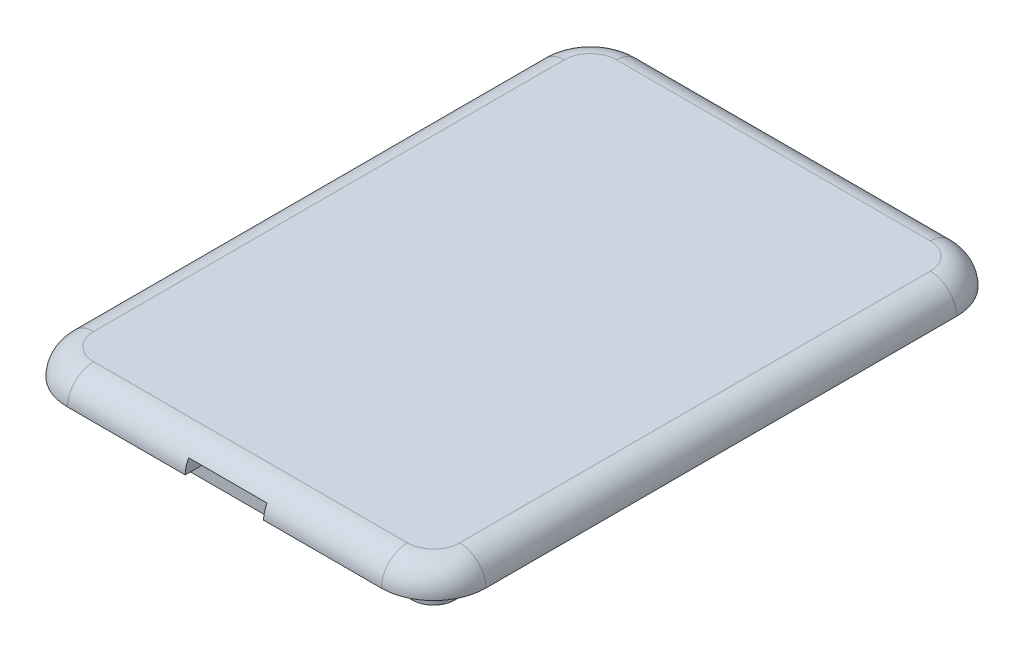
SolidWorks part; units mm, degrees
ref_plane "Front Plane" through (0, 0, 0) normal (0, 0, 1) x (1, 0, 0)
ref_plane "Top Plane" through (0, 0, 0) normal (0, 1, 0) x (1, 0, 0)
ref_plane "Right Plane" through (0, 0, 0) normal (1, 0, 0) x (0, 0, -1)
sketch "Sketch1" plane through (0, 0, 0) normal (0, 1, 0) x (1, 0, 0)
  line L0 (-45.2395, 52.3807) -> (-45.2395, -61.9193)
  line L1 (-40.1595, 65.0807) -> (36.0405, 65.0807)
  line L2 (-52.8595, 52.3807) -> (-52.8595, -61.9193)
  line L3 (-40.1595, -74.6193) -> (36.0405, -74.6193)
  line L4 (48.7405, 52.3807) -> (48.7405, -61.9193)
  line L5 (-40.1595, -66.9993) -> (36.0405, -66.9993)
  line L6 (41.1205, 52.3807) -> (41.1205, -61.9193)
  line L7 (-40.1595, 57.4607) -> (36.0405, 57.4607)
  line L8 (-37.6195, 49.8407) -> (-37.6195, -59.3793)
  line L9 (-37.6195, -59.3793) -> (33.5005, -59.3793)
  line L10 (33.5005, 49.8407) -> (33.5005, -59.3793)
  line L11 (-37.6195, 49.8407) -> (33.5005, 49.8407)
  arc A0 (-52.8595, -61.9193) -> (-40.1595, -74.6193) centre (-40.1595, -61.9193) ccw
  arc A1 (36.0405, -74.6193) -> (48.7405, -61.9193) centre (36.0405, -61.9193) ccw
  arc A2 (36.0405, 65.0807) -> (48.7405, 52.3807) centre (36.0405, 52.3807) cw
  arc A3 (-40.1595, 65.0807) -> (-52.8595, 52.3807) centre (-40.1595, 52.3807) ccw
  arc A4 (-45.2395, -61.9193) -> (-40.1595, -66.9993) centre (-40.1595, -61.9193) ccw
  arc A5 (36.0405, -66.9993) -> (41.1205, -61.9193) centre (36.0405, -61.9193) ccw
  arc A6 (36.0405, 57.4607) -> (41.1205, 52.3807) centre (36.0405, 52.3807) cw
  arc A7 (-40.1595, 57.4607) -> (-45.2395, 52.3807) centre (-40.1595, 52.3807) ccw
  arc A8 (-37.6195, -59.3793) -> (-37.6195, -59.3793) centre (-37.6195, -59.3793) ccw
  arc A9 (33.5005, -59.3793) -> (33.5005, -59.3793) centre (33.5005, -59.3793) ccw
  arc A10 (33.5005, 49.8407) -> (33.5005, 49.8407) centre (33.5005, 49.8407) cw
  arc A11 (-37.6195, 49.8407) -> (-37.6195, 49.8407) centre (-37.6195, 49.8407) ccw
  point P6 (-52.8595, -74.6193)
  point P9 (48.7405, -74.6193)
  point P14 (-52.8595, 65.0807)
  dimension "D3" = 12.7
  dimension "D1" = 139.7
  dimension "D2" = 101.6
  dimension "D4" = 7.62
  dimension "D5" = 7.62
extrude "Boss-Extrude1" add sketch "Sketch1" against normal blind 6.35 contours L7 A7 L0 A4 L5 A5 L6 A6 L8 L11 L10 L9 region at (-42.6804, 0, -54.9017)
extrude "Boss-Extrude3" add sketch "Sketch1<4>" along normal blind 6.35 contours L2 A0 L3 A1 L4 A2 L1 A3
sketch "Sketch1<4>" plane through (0, 0, 0) normal (0, 1, 0) x (1, 0, 0) same geometry as "Sketch1"
fillet "Fillet1" radius 6.35 8 edges at (-49.1397, 6.35, -61.361) (-2.0595, 6.35, -65.0807) (45.0208, 6.35, -61.361) (48.7405, 6.35, 4.7693) (45.0208, 6.35, 70.8995) (-2.0595, 6.35, 74.6193) (-49.1397, 6.35, 70.8995) (-52.8595, 6.35, 4.7693)
ref_plane "Plane2" through (0, 0, 74.6193) normal (0, 0, 1) x (1, 0, 0)
sketch "Sketch3" plane through (0, 0, 74.6193) normal (0, 0, 1) x (1, 0, 0)
  line L0 (-40.1595, 0) -> (36.0405, 0) construction
  line L1 (-11.5845, 3.175) -> (7.4655, 3.175)
  line L2 (-11.5845, 3.175) -> (-11.5845, -3.175)
  line L3 (-11.5845, -3.175) -> (7.4655, -3.175)
  line L4 (7.4655, 3.175) -> (7.4655, -3.175)
  line L5 (-11.5845, 3.175) -> (7.4655, -3.175) construction
  line L6 (-11.5845, -3.175) -> (7.4655, 3.175) construction
  line L7 (-40.1595, 0) -> (36.0405, 0) construction
  point P0 (-2.0595, 0)
  point P7 (0, 0)
  dimension "D1" = 6.35
  dimension "D2" = 19.05
extrude "Cut-Extrude1" cut sketch "Sketch3" against normal blind 6.35 contours L2 L3 L4 L1
